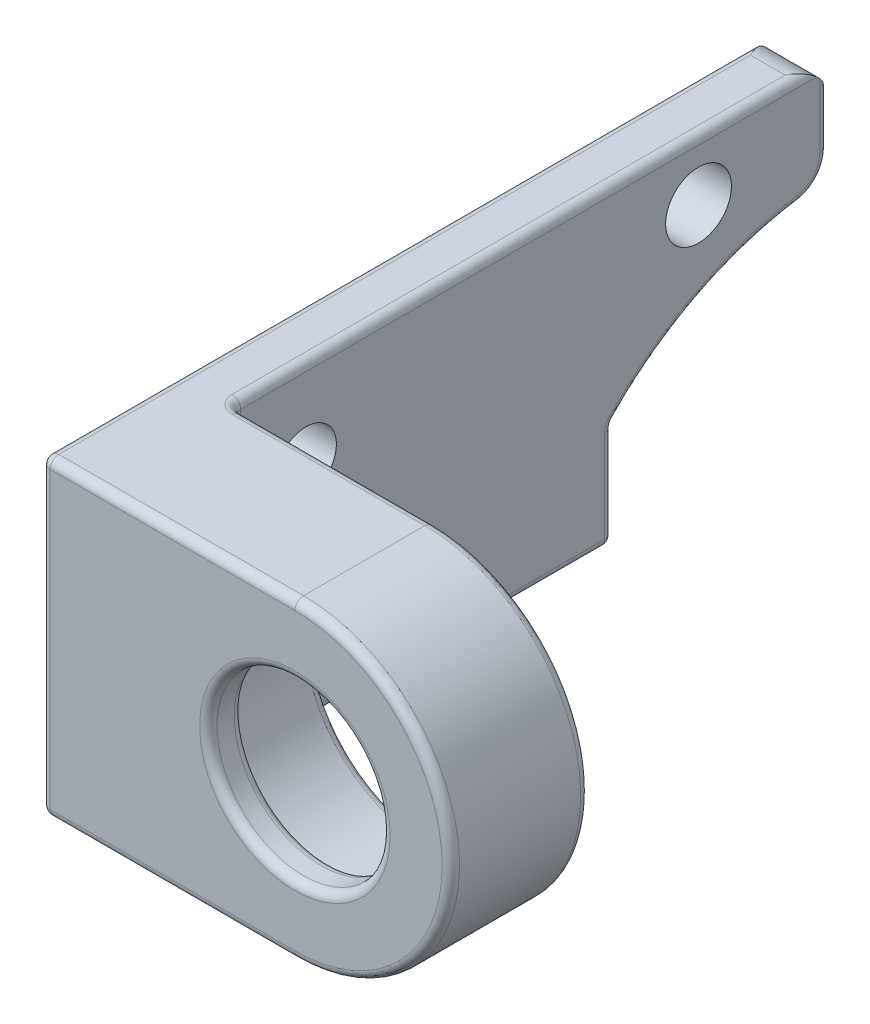
SolidWorks part; units mm, degrees
ref_plane "Front Plane" through (0, 0, 0) normal (0, 0, 1) x (1, 0, 0)
ref_plane "Top Plane" through (0, 0, 0) normal (0, 1, 0) x (1, 0, 0)
ref_plane "Right Plane" through (0, 0, 0) normal (1, 0, 0) x (0, 0, -1)
sketch "Sketch2" plane through (0, 0, 0) normal (0, 0, 1) x (1, 0, 0)
  line L0 (0, -9) -> (-14.6273, -9)
  line L1 (-14.6273, -9) -> (-14.6273, 9)
  line L2 (-14.6273, 9) -> (0, 9)
  circle A1 centre (0, 0) radius 6.9
  arc A2 (0, -9) -> (0, 9) centre (0, 0) ccw
  dimension "D1" = 18
  dimension "D2" = 13.8
extrude "Boss-Extrude1" add sketch "Sketch2" against normal blind 6 and the other way blind 2
sketch "Sketch3" plane through (0, 0, 2) normal (0, 0, 1) x (1, 0, 0)
  circle A0 centre (0, 0) radius 7.7988
  circle A1 centre (0, 0) radius 5
  dimension "D1" = 10
extrude "Boss-Extrude2" add sketch "Sketch3" against normal blind 2
sketch "Sketch4" plane through (0, 0, -6) normal (0, 0, -1) x (-1, 0, 0)
  line L0 (11.6273, 9) -> (11.6273, -9)
  line L3 (0, -9) -> (14.6273, -9)
  line L4 (14.6273, -9) -> (14.6273, 9)
  line L5 (14.6273, 9) -> (0, 9)
  line L6 (11.6273, -9) -> (14.6273, -9)
  line L7 (14.6273, -9) -> (14.6273, 9)
  line L8 (14.6273, 9) -> (11.6273, 9)
  arc A1 (0, 9) -> (0, -9) centre (0, 0) ccw
  dimension "D2" = 3
  dimension "D1" = 0
extrude "Boss-Extrude3" add sketch "Sketch4" along normal blind 22
sketch "Sketch6" plane through (-11.6273, 0, 0) normal (1, 0, 0) x (0, 0, -1)
  line L4 (28, 0) -> (37.2015, 0) construction
  line L5 (28, -2.9799) -> (28, 9)
  line L6 (38.4273, 9) -> (28, 9)
  line L7 (40.4273, 4.6299) -> (40.4273, 7)
  arc A2 (38.745, 2.6553) -> (40.4273, 4.6299) centre (38.4273, 4.6299) ccw
  arc A3 (40.4273, 7) -> (38.4273, 9) centre (38.4273, 7) ccw
  spline S1 degree 3 poles (28, -2.9799) (30.9408, 0.079) (34.5768, 1.9846) (38.745, 2.6553) knots 0 0 0 0 0.883331 0.883331 0.883331 0.883331
extrude "Boss-Extrude4" add sketch "Sketch6" against normal blind 3
sketch "Sketch5" plane through (-11.6273, 0, 0) normal (1, 0, 0) x (0, 0, -1)
  line L0 (38.4273, 9) -> (6, 9) construction
  line L1 (28, -9) -> (6, -9) construction
  line L4 (40.4273, 4.6299) -> (40.4273, 7) construction
  line L5 (38.4273, 9) -> (6, 9) construction
  circle A0 centre (10.2706, 4) radius 1.75
  circle A1 centre (10.2706, -4) radius 1.75
  circle A2 centre (32.9273, 5.5) radius 1.9
  dimension "D1" = 3.5
  dimension "D2" = 5
  dimension "D3" = 3.5
  dimension "D4" = 5
  dimension "D5" = 3.8
  dimension "D6" = 3.5
  dimension "D7" = 7.5
extrude "Cut-Extrude1" cut sketch "Sketch5" against normal blind 22
fillet "Fillet1" radius 0.5 21 edges at (-11.6273, -5.99, -28) (-14.6273, -5.99, -28) (5, 0, 2) (-7.3136, -9, 2) (-14.6273, 0, 2) (-7.3136, 9, 2) (9, 0, 2) (-5.8136, -9, -6) (9, 0, -6) (-5.8136, 9, -6) (-11.6273, 0, -6) (6.9, 0, -6) (-14.6273, 9, -18.2136) (-11.6273, 9, -22.2136) (-14.6273, -9, -13) (-11.6273, -9, -17) (5, 0, 0) (-13.1273, -9, -28) (-13.1273, -2.9799, -28) (-11.6273, 5.815, -40.4273) (-14.6273, 5.815, -40.4273)
fillet "Fillet2" radius 0.5 4 edges at (-14.6273, 2.8784, -39.3928) (-11.6273, 2.8784, -39.3928)
